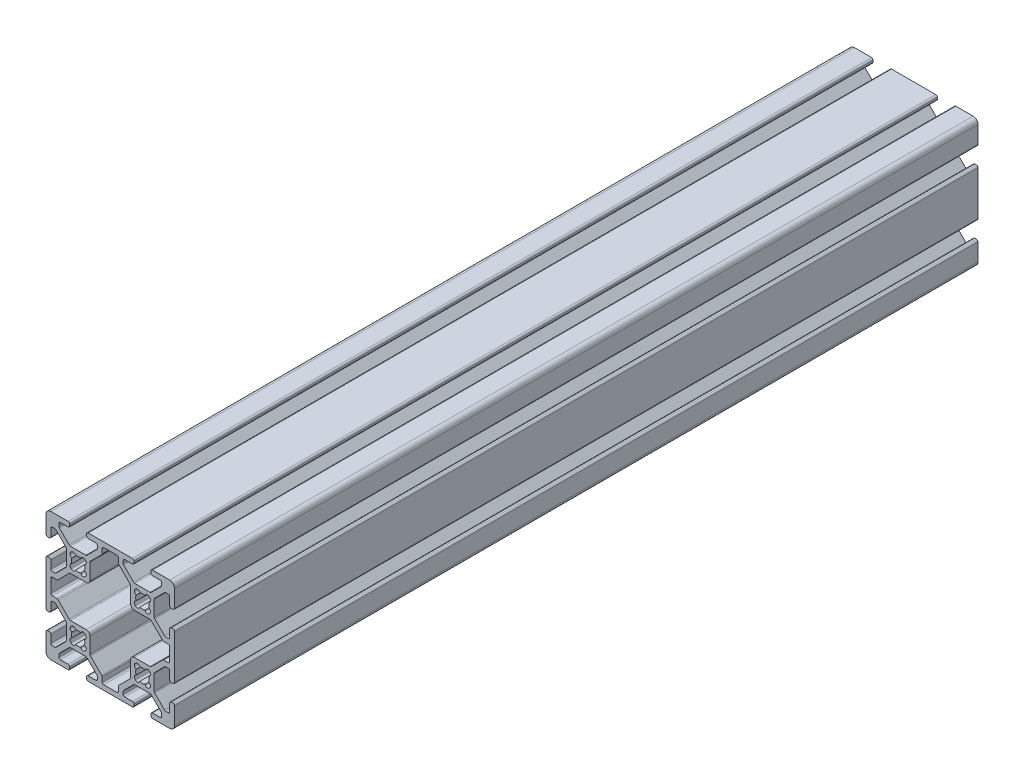
SolidWorks part; units mm, degrees
material "6105-T5 Aluminum"
ref_plane "Front Plane" through (0, 0, 0) normal (0, 0, 1) x (1, 0, 0)
ref_plane "Top Plane" through (0, 0, 0) normal (0, 1, 0) x (1, 0, 0)
ref_plane "Right Plane" through (0, 0, 0) normal (1, 0, 0) x (0, 0, -1)
sketch "Sketch1" plane through (0, 0, 0) normal (0, 0, 1) x (1, 0, 0)
  line L0 (-2.1249, 17.6955) -> (-2.3045, 17.8751)
  line L1 (-2.3045, 22.1249) -> (-2.1249, 22.3045)
  line L2 (2.1249, 22.3045) -> (2.3045, 22.1249)
  line L3 (2.3045, 17.8751) -> (2.1249, 17.6955)
  line L4 (-22.1249, 17.6955) -> (-22.3045, 17.8751)
  line L5 (-22.3045, 22.1249) -> (-22.1249, 22.3045)
  line L6 (-17.8751, 22.3045) -> (-17.6955, 22.1249)
  line L7 (-17.6955, 17.8751) -> (-17.8751, 17.6955)
  line L8 (-2.1249, -2.3045) -> (-2.3045, -2.1249)
  line L9 (-2.3045, 2.1249) -> (-2.1249, 2.3045)
  line L10 (2.1249, 2.3045) -> (2.3045, 2.1249)
  line L11 (2.3045, -2.1249) -> (2.1249, -2.3045)
  line L12 (-12.505, -7.992) -> (-12.505, -6.6448)
  line L13 (-12.6538, -6.2856) -> (-16.1962, -2.7431)
  line L14 (-16.345, -2.3839) -> (-16.345, 2.512)
  line L15 (-17.488, 3.655) -> (-22.3839, 3.655)
  line L16 (-22.7431, 3.8038) -> (-26.2856, 7.3462)
  line L17 (-26.6448, 7.495) -> (-27.992, 7.495)
  line L18 (-28.5, 8.003) -> (-28.5, 11.997)
  line L19 (-27.992, 12.505) -> (-26.6448, 12.505)
  line L20 (-26.2856, 12.6538) -> (-22.7431, 16.1962)
  line L21 (-22.3839, 16.345) -> (-17.488, 16.345)
  line L22 (-16.345, 17.488) -> (-16.345, 22.3839)
  line L23 (-16.1962, 22.7431) -> (-12.6538, 26.2856)
  line L24 (-12.505, 26.6448) -> (-12.505, 27.992)
  line L25 (-11.997, 28.5) -> (-8.003, 28.5)
  line L26 (-7.495, 27.992) -> (-7.495, 26.6448)
  line L27 (-7.3462, 26.2856) -> (-3.8038, 22.7431)
  line L28 (-3.655, 22.3839) -> (-3.655, 17.488)
  line L29 (-2.512, 16.345) -> (2.3839, 16.345)
  line L30 (2.7431, 16.1962) -> (6.2856, 12.6538)
  line L31 (6.6448, 12.505) -> (7.992, 12.505)
  line L32 (8.5, 11.997) -> (8.5, 8.003)
  line L33 (7.992, 7.495) -> (6.6448, 7.495)
  line L34 (6.2856, 7.3462) -> (2.7431, 3.8038)
  line L35 (2.3839, 3.655) -> (-2.512, 3.655)
  line L36 (-3.655, 2.512) -> (-3.655, -2.3839)
  line L37 (-3.8038, -2.7431) -> (-7.3462, -6.2856)
  line L38 (-7.495, -6.6448) -> (-7.495, -7.992)
  line L39 (-8.003, -8.5) -> (-11.997, -8.5)
  line L40 (-22.1249, -2.3045) -> (-22.3045, -2.1249)
  line L41 (-22.3045, 2.1249) -> (-22.1249, 2.3045)
  line L42 (-17.8751, 2.3045) -> (-17.6955, 2.1249)
  line L43 (-17.6955, -2.1249) -> (-17.8751, -2.3045)
  line L44 (-22.3839, -3.655) -> (-17.6161, -3.655)
  line L45 (-17.2569, -3.8038) -> (-14.1538, -6.9069)
  line L46 (-14.005, -7.2661) -> (-14.005, -7.992)
  line L47 (-14.513, -8.5) -> (-16.862, -8.5)
  line L48 (-17.37, -9.008) -> (-17.37, -9.492)
  line L49 (-16.862, -10) -> (-3.138, -10)
  line L50 (-2.63, -9.492) -> (-2.63, -9.008)
  line L51 (-3.138, -8.5) -> (-5.487, -8.5)
  line L52 (-5.995, -7.992) -> (-5.995, -7.2661)
  line L53 (-5.8462, -6.9069) -> (-2.7431, -3.8038)
  line L54 (-2.3839, -3.655) -> (2.3839, -3.655)
  line L55 (2.7431, -3.8038) -> (5.8462, -6.9069)
  line L56 (5.995, -7.2661) -> (5.995, -7.992)
  line L57 (5.487, -8.5) -> (3.138, -8.5)
  line L58 (2.63, -9.008) -> (2.63, -9.492)
  line L59 (3.138, -10) -> (8.5, -10)
  line L60 (10, -8.5) -> (10, -3.138)
  line L61 (9.492, -2.63) -> (9.008, -2.63)
  line L62 (8.5, -3.138) -> (8.5, -5.487)
  line L63 (7.992, -5.995) -> (7.2661, -5.995)
  line L64 (6.9069, -5.8462) -> (3.8038, -2.7431)
  line L65 (3.655, -2.3839) -> (3.655, 2.3839)
  line L66 (3.8038, 2.7431) -> (6.9069, 5.8462)
  line L67 (7.2661, 5.995) -> (7.992, 5.995)
  line L68 (8.5, 5.487) -> (8.5, 3.138)
  line L69 (9.008, 2.63) -> (9.492, 2.63)
  line L70 (10, 3.138) -> (10, 16.862)
  line L71 (9.492, 17.37) -> (9.008, 17.37)
  line L72 (8.5, 16.862) -> (8.5, 14.513)
  line L73 (7.992, 14.005) -> (7.2661, 14.005)
  line L74 (6.9069, 14.1538) -> (3.8038, 17.2569)
  line L75 (3.655, 17.6161) -> (3.655, 22.3839)
  line L76 (3.8038, 22.7431) -> (6.9069, 25.8462)
  line L77 (7.2661, 25.995) -> (7.992, 25.995)
  line L78 (8.5, 25.487) -> (8.5, 23.138)
  line L79 (9.008, 22.63) -> (9.492, 22.63)
  line L80 (10, 23.138) -> (10, 28.5)
  line L81 (8.5, 30) -> (3.138, 30)
  line L82 (2.63, 29.492) -> (2.63, 29.008)
  line L83 (3.138, 28.5) -> (5.487, 28.5)
  line L84 (5.995, 27.992) -> (5.995, 27.2661)
  line L85 (5.8462, 26.9069) -> (2.7431, 23.8038)
  line L86 (2.3839, 23.655) -> (-2.3839, 23.655)
  line L87 (-2.7431, 23.8038) -> (-5.8462, 26.9069)
  line L88 (-5.995, 27.2661) -> (-5.995, 27.992)
  line L89 (-5.487, 28.5) -> (-3.138, 28.5)
  line L90 (-2.63, 29.008) -> (-2.63, 29.492)
  line L91 (-3.138, 30) -> (-16.862, 30)
  line L92 (-17.37, 29.492) -> (-17.37, 29.008)
  line L93 (-16.862, 28.5) -> (-14.513, 28.5)
  line L94 (-14.005, 27.992) -> (-14.005, 27.2661)
  line L95 (-14.1538, 26.9069) -> (-17.2569, 23.8038)
  line L96 (-17.6161, 23.655) -> (-22.3839, 23.655)
  line L97 (-22.7431, 23.8038) -> (-25.8462, 26.9069)
  line L98 (-25.995, 27.2661) -> (-25.995, 27.992)
  line L99 (-25.487, 28.5) -> (-23.138, 28.5)
  line L100 (-22.63, 29.008) -> (-22.63, 29.492)
  line L101 (-23.138, 30) -> (-28.5, 30)
  line L102 (-30, 28.5) -> (-30, 23.138)
  line L103 (-29.492, 22.63) -> (-29.008, 22.63)
  line L104 (-28.5, 23.138) -> (-28.5, 25.487)
  line L105 (-27.992, 25.995) -> (-27.2661, 25.995)
  line L106 (-26.9069, 25.8462) -> (-23.8038, 22.7431)
  line L107 (-23.655, 22.3839) -> (-23.655, 17.6161)
  line L108 (-23.8038, 17.2569) -> (-26.9069, 14.1538)
  line L109 (-27.2661, 14.005) -> (-27.992, 14.005)
  line L110 (-28.5, 14.513) -> (-28.5, 16.862)
  line L111 (-29.008, 17.37) -> (-29.492, 17.37)
  line L112 (-30, 16.862) -> (-30, 3.138)
  line L113 (-29.492, 2.63) -> (-29.008, 2.63)
  line L114 (-28.5, 3.138) -> (-28.5, 5.487)
  line L115 (-27.992, 5.995) -> (-27.2661, 5.995)
  line L116 (-26.9069, 5.8462) -> (-23.8038, 2.7431)
  line L117 (-23.655, 2.3839) -> (-23.655, -2.3839)
  line L118 (-23.8038, -2.7431) -> (-26.9069, -5.8462)
  line L119 (-27.2661, -5.995) -> (-27.992, -5.995)
  line L120 (-28.5, -5.487) -> (-28.5, -3.138)
  line L121 (-29.008, -2.63) -> (-29.492, -2.63)
  line L122 (-30, -3.138) -> (-30, -8.5)
  line L123 (-28.5, -10) -> (-23.138, -10)
  line L124 (-22.63, -9.492) -> (-22.63, -9.008)
  line L125 (-23.138, -8.5) -> (-25.487, -8.5)
  line L126 (-25.995, -7.992) -> (-25.995, -7.2661)
  line L127 (-25.8462, -6.9069) -> (-22.7431, -3.8038)
  arc A0 (-1.9351, 19.196) -> (-2.3045, 17.8751) centre (-1.748, 18.4316) ccw
  arc A1 (-1.9351, 20.804) -> (-1.9351, 19.196) centre (0, 20) ccw
  arc A2 (-2.3045, 22.1249) -> (-1.9351, 20.804) centre (-1.748, 21.5684) ccw
  arc A3 (-0.804, 21.9351) -> (-2.1249, 22.3045) centre (-1.5684, 21.748) ccw
  arc A4 (0.804, 21.9351) -> (-0.804, 21.9351) centre (0, 20) ccw
  arc A5 (2.1249, 22.3045) -> (0.804, 21.9351) centre (1.5684, 21.748) ccw
  arc A6 (1.9351, 20.804) -> (2.3045, 22.1249) centre (1.748, 21.5684) ccw
  arc A7 (1.9351, 19.196) -> (1.9351, 20.804) centre (0, 20) ccw
  arc A8 (2.3045, 17.8751) -> (1.9351, 19.196) centre (1.748, 18.4316) ccw
  arc A9 (0.804, 18.0649) -> (2.1249, 17.6955) centre (1.5684, 18.252) ccw
  arc A10 (-0.804, 18.0649) -> (0.804, 18.0649) centre (0, 20) ccw
  arc A11 (-2.1249, 17.6955) -> (-0.804, 18.0649) centre (-1.5684, 18.252) ccw
  arc A12 (-21.9351, 19.196) -> (-22.3045, 17.8751) centre (-21.748, 18.4316) ccw
  arc A13 (-21.9351, 20.804) -> (-21.9351, 19.196) centre (-20, 20) ccw
  arc A14 (-22.3045, 22.1249) -> (-21.9351, 20.804) centre (-21.748, 21.5684) ccw
  arc A15 (-20.804, 21.9351) -> (-22.1249, 22.3045) centre (-21.5684, 21.748) ccw
  arc A16 (-19.196, 21.9351) -> (-20.804, 21.9351) centre (-20, 20) ccw
  arc A17 (-17.8751, 22.3045) -> (-19.196, 21.9351) centre (-18.4316, 21.748) ccw
  arc A18 (-18.0649, 20.804) -> (-17.6955, 22.1249) centre (-18.252, 21.5684) ccw
  arc A19 (-18.0649, 19.196) -> (-18.0649, 20.804) centre (-20, 20) ccw
  arc A20 (-17.6955, 17.8751) -> (-18.0649, 19.196) centre (-18.252, 18.4316) ccw
  arc A21 (-19.196, 18.0649) -> (-17.8751, 17.6955) centre (-18.4316, 18.252) ccw
  arc A22 (-20.804, 18.0649) -> (-19.196, 18.0649) centre (-20, 20) ccw
  arc A23 (-22.1249, 17.6955) -> (-20.804, 18.0649) centre (-21.5684, 18.252) ccw
  arc A24 (-1.9351, -0.804) -> (-2.3045, -2.1249) centre (-1.748, -1.5684) ccw
  arc A25 (-1.9351, 0.804) -> (-1.9351, -0.804) centre (0, 0) ccw
  arc A26 (-2.3045, 2.1249) -> (-1.9351, 0.804) centre (-1.748, 1.5684) ccw
  arc A27 (-0.804, 1.9351) -> (-2.1249, 2.3045) centre (-1.5684, 1.748) ccw
  arc A28 (0.804, 1.9351) -> (-0.804, 1.9351) centre (0, 0) ccw
  arc A29 (2.1249, 2.3045) -> (0.804, 1.9351) centre (1.5684, 1.748) ccw
  arc A30 (1.9351, 0.804) -> (2.3045, 2.1249) centre (1.748, 1.5684) ccw
  arc A31 (1.9351, -0.804) -> (1.9351, 0.804) centre (0, 0) ccw
  arc A32 (2.3045, -2.1249) -> (1.9351, -0.804) centre (1.748, -1.5684) ccw
  arc A33 (0.804, -1.9351) -> (2.1249, -2.3045) centre (1.5684, -1.748) ccw
  arc A34 (-0.804, -1.9351) -> (0.804, -1.9351) centre (0, 0) ccw
  arc A35 (-2.1249, -2.3045) -> (-0.804, -1.9351) centre (-1.5684, -1.748) ccw
  arc A36 (-12.505, -7.992) -> (-11.997, -8.5) centre (-11.997, -7.992) ccw
  arc A37 (-12.505, -6.6448) -> (-12.6538, -6.2856) centre (-13.013, -6.6448) ccw
  arc A38 (-16.345, -2.3839) -> (-16.1962, -2.7431) centre (-15.837, -2.3839) ccw
  arc A39 (-16.345, 2.512) -> (-17.488, 3.655) centre (-17.488, 2.512) ccw
  arc A40 (-22.7431, 3.8038) -> (-22.3839, 3.655) centre (-22.3839, 4.163) ccw
  arc A41 (-26.2856, 7.3462) -> (-26.6448, 7.495) centre (-26.6448, 6.987) ccw
  arc A42 (-28.5, 8.003) -> (-27.992, 7.495) centre (-27.992, 8.003) ccw
  arc A43 (-27.992, 12.505) -> (-28.5, 11.997) centre (-27.992, 11.997) ccw
  arc A44 (-26.6448, 12.505) -> (-26.2856, 12.6538) centre (-26.6448, 13.013) ccw
  arc A45 (-22.3839, 16.345) -> (-22.7431, 16.1962) centre (-22.3839, 15.837) ccw
  arc A46 (-17.488, 16.345) -> (-16.345, 17.488) centre (-17.488, 17.488) ccw
  arc A47 (-16.1962, 22.7431) -> (-16.345, 22.3839) centre (-15.837, 22.3839) ccw
  arc A48 (-12.6538, 26.2856) -> (-12.505, 26.6448) centre (-13.013, 26.6448) ccw
  arc A49 (-11.997, 28.5) -> (-12.505, 27.992) centre (-11.997, 27.992) ccw
  arc A50 (-7.495, 27.992) -> (-8.003, 28.5) centre (-8.003, 27.992) ccw
  arc A51 (-7.495, 26.6448) -> (-7.3462, 26.2856) centre (-6.987, 26.6448) ccw
  arc A52 (-3.655, 22.3839) -> (-3.8038, 22.7431) centre (-4.163, 22.3839) ccw
  arc A53 (-3.655, 17.488) -> (-2.512, 16.345) centre (-2.512, 17.488) ccw
  arc A54 (2.7431, 16.1962) -> (2.3839, 16.345) centre (2.3839, 15.837) ccw
  arc A55 (6.2856, 12.6538) -> (6.6448, 12.505) centre (6.6448, 13.013) ccw
  arc A56 (8.5, 11.997) -> (7.992, 12.505) centre (7.992, 11.997) ccw
  arc A57 (7.992, 7.495) -> (8.5, 8.003) centre (7.992, 8.003) ccw
  arc A58 (6.6448, 7.495) -> (6.2856, 7.3462) centre (6.6448, 6.987) ccw
  arc A59 (2.3839, 3.655) -> (2.7431, 3.8038) centre (2.3839, 4.163) ccw
  arc A60 (-2.512, 3.655) -> (-3.655, 2.512) centre (-2.512, 2.512) ccw
  arc A61 (-3.8038, -2.7431) -> (-3.655, -2.3839) centre (-4.163, -2.3839) ccw
  arc A62 (-7.3462, -6.2856) -> (-7.495, -6.6448) centre (-6.987, -6.6448) ccw
  arc A63 (-8.003, -8.5) -> (-7.495, -7.992) centre (-8.003, -7.992) ccw
  arc A64 (-21.9351, -0.804) -> (-22.3045, -2.1249) centre (-21.748, -1.5684) ccw
  arc A65 (-21.9351, 0.804) -> (-21.9351, -0.804) centre (-20, 0) ccw
  arc A66 (-22.3045, 2.1249) -> (-21.9351, 0.804) centre (-21.748, 1.5684) ccw
  arc A67 (-20.804, 1.9351) -> (-22.1249, 2.3045) centre (-21.5684, 1.748) ccw
  arc A68 (-19.196, 1.9351) -> (-20.804, 1.9351) centre (-20, 0) ccw
  arc A69 (-17.8751, 2.3045) -> (-19.196, 1.9351) centre (-18.4316, 1.748) ccw
  arc A70 (-18.0649, 0.804) -> (-17.6955, 2.1249) centre (-18.252, 1.5684) ccw
  arc A71 (-18.0649, -0.804) -> (-18.0649, 0.804) centre (-20, 0) ccw
  arc A72 (-17.6955, -2.1249) -> (-18.0649, -0.804) centre (-18.252, -1.5684) ccw
  arc A73 (-19.196, -1.9351) -> (-17.8751, -2.3045) centre (-18.4316, -1.748) ccw
  arc A74 (-20.804, -1.9351) -> (-19.196, -1.9351) centre (-20, 0) ccw
  arc A75 (-22.1249, -2.3045) -> (-20.804, -1.9351) centre (-21.5684, -1.748) ccw
  arc A76 (-22.3839, -3.655) -> (-22.7431, -3.8038) centre (-22.3839, -4.163) ccw
  arc A77 (-17.2569, -3.8038) -> (-17.6161, -3.655) centre (-17.6161, -4.163) ccw
  arc A78 (-14.005, -7.2661) -> (-14.1538, -6.9069) centre (-14.513, -7.2661) ccw
  arc A79 (-14.513, -8.5) -> (-14.005, -7.992) centre (-14.513, -7.992) ccw
  arc A80 (-16.862, -8.5) -> (-17.37, -9.008) centre (-16.862, -9.008) ccw
  arc A81 (-17.37, -9.492) -> (-16.862, -10) centre (-16.862, -9.492) ccw
  arc A82 (-3.138, -10) -> (-2.63, -9.492) centre (-3.138, -9.492) ccw
  arc A83 (-2.63, -9.008) -> (-3.138, -8.5) centre (-3.138, -9.008) ccw
  arc A84 (-5.995, -7.992) -> (-5.487, -8.5) centre (-5.487, -7.992) ccw
  arc A85 (-5.8462, -6.9069) -> (-5.995, -7.2661) centre (-5.487, -7.2661) ccw
  arc A86 (-2.3839, -3.655) -> (-2.7431, -3.8038) centre (-2.3839, -4.163) ccw
  arc A87 (2.7431, -3.8038) -> (2.3839, -3.655) centre (2.3839, -4.163) ccw
  arc A88 (5.995, -7.2661) -> (5.8462, -6.9069) centre (5.487, -7.2661) ccw
  arc A89 (5.487, -8.5) -> (5.995, -7.992) centre (5.487, -7.992) ccw
  arc A90 (3.138, -8.5) -> (2.63, -9.008) centre (3.138, -9.008) ccw
  arc A91 (2.63, -9.492) -> (3.138, -10) centre (3.138, -9.492) ccw
  arc A92 (8.5, -10) -> (10, -8.5) centre (8.5, -8.5) ccw
  arc A93 (10, -3.138) -> (9.492, -2.63) centre (9.492, -3.138) ccw
  arc A94 (9.008, -2.63) -> (8.5, -3.138) centre (9.008, -3.138) ccw
  arc A95 (7.992, -5.995) -> (8.5, -5.487) centre (7.992, -5.487) ccw
  arc A96 (6.9069, -5.8462) -> (7.2661, -5.995) centre (7.2661, -5.487) ccw
  arc A97 (3.655, -2.3839) -> (3.8038, -2.7431) centre (4.163, -2.3839) ccw
  arc A98 (3.8038, 2.7431) -> (3.655, 2.3839) centre (4.163, 2.3839) ccw
  arc A99 (7.2661, 5.995) -> (6.9069, 5.8462) centre (7.2661, 5.487) ccw
  arc A100 (8.5, 5.487) -> (7.992, 5.995) centre (7.992, 5.487) ccw
  arc A101 (8.5, 3.138) -> (9.008, 2.63) centre (9.008, 3.138) ccw
  arc A102 (9.492, 2.63) -> (10, 3.138) centre (9.492, 3.138) ccw
  arc A103 (10, 16.862) -> (9.492, 17.37) centre (9.492, 16.862) ccw
  arc A104 (9.008, 17.37) -> (8.5, 16.862) centre (9.008, 16.862) ccw
  arc A105 (7.992, 14.005) -> (8.5, 14.513) centre (7.992, 14.513) ccw
  arc A106 (6.9069, 14.1538) -> (7.2661, 14.005) centre (7.2661, 14.513) ccw
  arc A107 (3.655, 17.6161) -> (3.8038, 17.2569) centre (4.163, 17.6161) ccw
  arc A108 (3.8038, 22.7431) -> (3.655, 22.3839) centre (4.163, 22.3839) ccw
  arc A109 (7.2661, 25.995) -> (6.9069, 25.8462) centre (7.2661, 25.487) ccw
  arc A110 (8.5, 25.487) -> (7.992, 25.995) centre (7.992, 25.487) ccw
  arc A111 (8.5, 23.138) -> (9.008, 22.63) centre (9.008, 23.138) ccw
  arc A112 (9.492, 22.63) -> (10, 23.138) centre (9.492, 23.138) ccw
  arc A113 (10, 28.5) -> (8.5, 30) centre (8.5, 28.5) ccw
  arc A114 (3.138, 30) -> (2.63, 29.492) centre (3.138, 29.492) ccw
  arc A115 (2.63, 29.008) -> (3.138, 28.5) centre (3.138, 29.008) ccw
  arc A116 (5.995, 27.992) -> (5.487, 28.5) centre (5.487, 27.992) ccw
  arc A117 (5.8462, 26.9069) -> (5.995, 27.2661) centre (5.487, 27.2661) ccw
  arc A118 (2.3839, 23.655) -> (2.7431, 23.8038) centre (2.3839, 24.163) ccw
  arc A119 (-2.7431, 23.8038) -> (-2.3839, 23.655) centre (-2.3839, 24.163) ccw
  arc A120 (-5.995, 27.2661) -> (-5.8462, 26.9069) centre (-5.487, 27.2661) ccw
  arc A121 (-5.487, 28.5) -> (-5.995, 27.992) centre (-5.487, 27.992) ccw
  arc A122 (-3.138, 28.5) -> (-2.63, 29.008) centre (-3.138, 29.008) ccw
  arc A123 (-2.63, 29.492) -> (-3.138, 30) centre (-3.138, 29.492) ccw
  arc A124 (-16.862, 30) -> (-17.37, 29.492) centre (-16.862, 29.492) ccw
  arc A125 (-17.37, 29.008) -> (-16.862, 28.5) centre (-16.862, 29.008) ccw
  arc A126 (-14.005, 27.992) -> (-14.513, 28.5) centre (-14.513, 27.992) ccw
  arc A127 (-14.1538, 26.9069) -> (-14.005, 27.2661) centre (-14.513, 27.2661) ccw
  arc A128 (-17.6161, 23.655) -> (-17.2569, 23.8038) centre (-17.6161, 24.163) ccw
  arc A129 (-22.7431, 23.8038) -> (-22.3839, 23.655) centre (-22.3839, 24.163) ccw
  arc A130 (-25.995, 27.2661) -> (-25.8462, 26.9069) centre (-25.487, 27.2661) ccw
  arc A131 (-25.487, 28.5) -> (-25.995, 27.992) centre (-25.487, 27.992) ccw
  arc A132 (-23.138, 28.5) -> (-22.63, 29.008) centre (-23.138, 29.008) ccw
  arc A133 (-22.63, 29.492) -> (-23.138, 30) centre (-23.138, 29.492) ccw
  arc A134 (-28.5, 30) -> (-30, 28.5) centre (-28.5, 28.5) ccw
  arc A135 (-30, 23.138) -> (-29.492, 22.63) centre (-29.492, 23.138) ccw
  arc A136 (-29.008, 22.63) -> (-28.5, 23.138) centre (-29.008, 23.138) ccw
  arc A137 (-27.992, 25.995) -> (-28.5, 25.487) centre (-27.992, 25.487) ccw
  arc A138 (-26.9069, 25.8462) -> (-27.2661, 25.995) centre (-27.2661, 25.487) ccw
  arc A139 (-23.655, 22.3839) -> (-23.8038, 22.7431) centre (-24.163, 22.3839) ccw
  arc A140 (-23.8038, 17.2569) -> (-23.655, 17.6161) centre (-24.163, 17.6161) ccw
  arc A141 (-27.2661, 14.005) -> (-26.9069, 14.1538) centre (-27.2661, 14.513) ccw
  arc A142 (-28.5, 14.513) -> (-27.992, 14.005) centre (-27.992, 14.513) ccw
  arc A143 (-28.5, 16.862) -> (-29.008, 17.37) centre (-29.008, 16.862) ccw
  arc A144 (-29.492, 17.37) -> (-30, 16.862) centre (-29.492, 16.862) ccw
  arc A145 (-30, 3.138) -> (-29.492, 2.63) centre (-29.492, 3.138) ccw
  arc A146 (-29.008, 2.63) -> (-28.5, 3.138) centre (-29.008, 3.138) ccw
  arc A147 (-27.992, 5.995) -> (-28.5, 5.487) centre (-27.992, 5.487) ccw
  arc A148 (-26.9069, 5.8462) -> (-27.2661, 5.995) centre (-27.2661, 5.487) ccw
  arc A149 (-23.655, 2.3839) -> (-23.8038, 2.7431) centre (-24.163, 2.3839) ccw
  arc A150 (-23.8038, -2.7431) -> (-23.655, -2.3839) centre (-24.163, -2.3839) ccw
  arc A151 (-27.2661, -5.995) -> (-26.9069, -5.8462) centre (-27.2661, -5.487) ccw
  arc A152 (-28.5, -5.487) -> (-27.992, -5.995) centre (-27.992, -5.487) ccw
  arc A153 (-28.5, -3.138) -> (-29.008, -2.63) centre (-29.008, -3.138) ccw
  arc A154 (-29.492, -2.63) -> (-30, -3.138) centre (-29.492, -3.138) ccw
  arc A155 (-30, -8.5) -> (-28.5, -10) centre (-28.5, -8.5) ccw
  arc A156 (-23.138, -10) -> (-22.63, -9.492) centre (-23.138, -9.492) ccw
  arc A157 (-22.63, -9.008) -> (-23.138, -8.5) centre (-23.138, -9.008) ccw
  arc A158 (-25.995, -7.992) -> (-25.487, -8.5) centre (-25.487, -7.992) ccw
  arc A159 (-25.8462, -6.9069) -> (-25.995, -7.2661) centre (-25.487, -7.2661) ccw
extrude "Extrude1" add sketch "Sketch1" against normal blind 250
